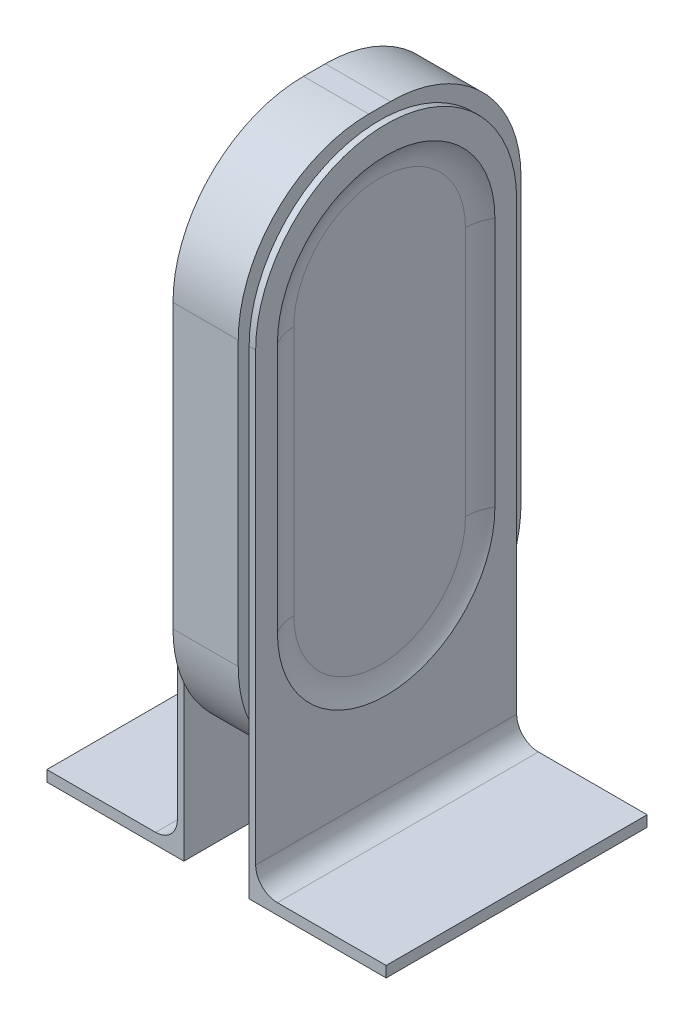
SolidWorks part; units mm, degrees
note: The reader was unsure of these and kept them because the rebuilt part matched: shared geometry of "Sketch3<4>".
ref_plane "Front Plane" through (0, 0, 0) normal (0, 0, 1) x (1, 0, 0)
ref_plane "Top Plane" through (0, 0, 0) normal (0, 1, 0) x (1, 0, 0)
ref_plane "Right Plane" through (0, 0, 0) normal (1, 0, 0) x (0, 0, -1)
sketch "Sketch1" plane through (0, 0, 0) normal (1, 0, 0) x (0, 0, -1)
  line L1 (5, 125) -> (-5, 125)
  line L2 (65, 65) -> (65, -65)
  line L3 (5, -125) -> (-5, -125)
  line L4 (-65, 65) -> (-65, -65)
  line L5 (65, 125) -> (-65, -125) construction
  line L6 (65, -125) -> (-65, 125) construction
  arc A0 (-5, 125) -> (-65, 65) centre (-5, 65) ccw
  arc A1 (-5, -125) -> (-65, -65) centre (-5, -65) cw
  arc A2 (65, -65) -> (5, -125) centre (5, -65) cw
  arc A3 (5, 125) -> (65, 65) centre (5, 65) cw
  point P0 (0, 0)
  dimension "D3" = 60
  dimension "D1" = 250
  dimension "D2" = 130
extrude "Boss-Extrude1" add sketch "Sketch1" along normal mid plane 30
sketch "Sketch3" plane through (15, 0, 0) normal (1, 0, 0) x (0, 0, -1)
  line L0 (0, 125) -> (0, -125) construction
  line L1 (5, 125) -> (-5, 125) construction
  line L2 (-5, -125) -> (5, -125) construction
  line L3 (0, -60) -> (0, 60) construction
  line L4 (-60, -60) -> (-60, 60)
  line L5 (60, -60) -> (60, 60)
  line L6 (0, -57.5) -> (0, 57.5) construction
  line L7 (-50, -57.5) -> (-50, 57.5)
  line L8 (50, -57.5) -> (50, 57.5)
  line L9 (-60, -60) -> (-60, -160)
  line L10 (-60, -160) -> (60, -160)
  line L11 (60, -160) -> (60, -60)
  arc A1 (60, 60) -> (-60, 60) centre (0, 60) ccw
  arc A2 (-50, -57.5) -> (50, -57.5) centre (0, -57.5) ccw
  arc A3 (50, 57.5) -> (-50, 57.5) centre (0, 57.5) ccw
  point P6 (0, 0)
  point P16 (0, 0)
  point P21 (0, 0)
  point P23 (0, 0)
  point P25 (0, 125)
  point P26 (0, 0)
  point P27 (0, -60)
  dimension "D2" = 220
  dimension "D4" = 100
  dimension "D7" = 60
  dimension "D9" = 35
  dimension "D10" = 2.5
  dimension "D1" = 120
  dimension "D3" = 115
  dimension "D5" = 100
  dimension "D6" = 120
  dimension "D8" = 60
extrude "Boss-Extrude2" add sketch "Sketch3" along normal blind 3
fillet "Fillet1" radius 20 4 edges at (15, 0, -50) (15, -107.5, 0) (15, 0, 50) (15, 107.5, 0)
sketch "Sketch4" plane through (0, -160, 0) normal (0, -1, 0) x (1, 0, 0)
  line L0 (18, -60) -> (78, -60)
  line L1 (18, 60) -> (78, 60)
  line L2 (78, 60) -> (78, -60)
  line L3 (18, 60) -> (18, -60)
  line L4 (0, 65) -> (0, -65) construction
  line L5 (15, 65) -> (-15, 65) construction
  line L6 (15, -65) -> (-15, -65) construction
  line L7 (-18, 60) -> (-78, 60)
  line L8 (-78, 60) -> (-78, -60)
  line L9 (-18, -60) -> (-78, -60)
  line L10 (-18, 60) -> (-18, -60)
  point P9 (0, 65)
  point P12 (0, -65)
  dimension "D1" = 60
extrude "Boss-Extrude3" add sketch "Sketch4" against normal blind 5
extrude "Boss-Extrude4" add sketch "Sketch3<4>" against normal blind 3 from surface at -30
sketch "Sketch3<4>" plane through (15, 0, 0) normal (1, 0, 0) x (0, 0, -1) same geometry as "Sketch3"
fillet "Fillet2" radius 20 4 edges at (-15, -107.5, 0) (-15, 0, 50) (-15, 107.5, 0) (-15, 0, -50)
fillet "Fillet4" radius 10 1 edges at (18, -155, 0)
sketch "Sketch5" plane through (0, 0, 65) normal (0, 0, 1) x (1, 0, 0)
  line L0 (18, -145) -> (-18, -145) construction
  line L1 (-18, 60) -> (-18, -160) construction
  line L2 (28, -155) -> (28, -167.7796) construction
  line L3 (0, -129.4903) -> (0, -170.8987) construction
  line L4 (-28, -155) -> (-28, -167.7796) construction
  line L5 (-28, -155) -> (-18, -155)
  line L6 (-18, -155) -> (-18, -145)
  arc A1 (-28, -155) -> (-18, -145) centre (-28, -145) ccw
  dimension "D1" = 10
extrude "Boss-Extrude5" add sketch "Sketch5" against normal up to surface (120 mm away) from surface at -5 up to face at (-48, -157.5, -60) starting at face at (-16.2, -57.7958, 60)
